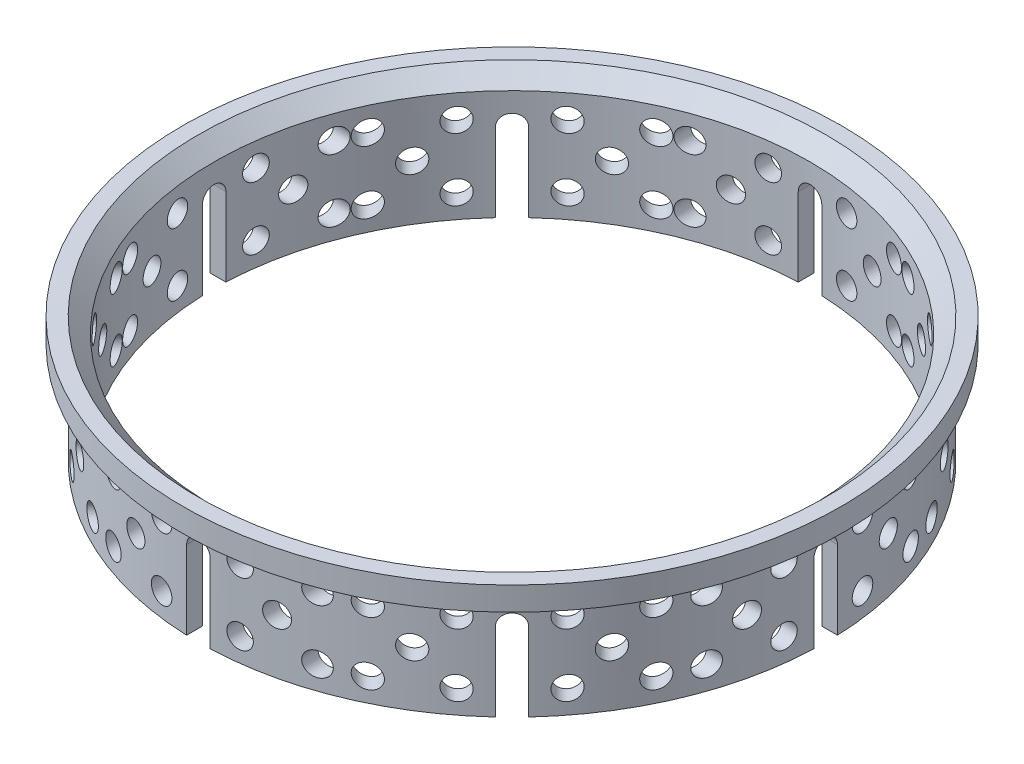
SolidWorks part; units mm, degrees
ref_plane "Front Plane" through (0, 0, 0) normal (0, 0, 1) x (1, 0, 0)
ref_plane "Top Plane" through (0, 0, 0) normal (0, 1, 0) x (1, 0, 0)
ref_plane "Right Plane" through (0, 0, 0) normal (1, 0, 0) x (0, 0, -1)
sketch "Sketch2" plane through (0, 0, 0) normal (0, 0, 1) x (1, 0, 0)
  line L0 (0, 0) -> (0, 28.4657) construction
  line L1 (0, 0) -> (48.26, 0) construction
  line L3 (53.34, 20.32) -> (53.34, 16.51)
  line L4 (53.34, 16.51) -> (50.8, 16.51)
  line L5 (50.8, 16.51) -> (50.8, 0)
  line L7 (48.26, 0) -> (50.8, 0)
  line L8 (48.26, 0) -> (48.26, 17.78)
  line L10 (53.34, 20.32) -> (50.8, 20.32)
  line L11 (50.8, 20.32) -> (48.26, 17.78)
  point P2 (0, 0)
  point P12 (0, 0)
  dimension "D1" = 48.26
  dimension "D2" = 17.78
  dimension "D3" = 2.54
  dimension "D4" = 3.81
  dimension "D5" = 2.54
  dimension "D6" = 2.54
revolve "Revolve1" add sketch "Sketch2" angle 360 about L0
ref_plane "Plane1" through (0, 0, 50.8) normal (0, 0, 1) x (1, 0, 0)
sketch "Sketch5" plane through (0, 0, 50.8) normal (0, 0, 1) x (1, 0, 0)
  line L0 (-1.905, 0) -> (1.905, 0)
  line L1 (-1.905, 0) -> (-1.905, 12.7)
  line L2 (1.905, 12.7) -> (1.905, 0)
  line L3 (-50.8, 0) -> (50.8, 0) construction
  line L4 (0, -11.176) -> (0, 11.176) construction
  arc A0 (-1.905, 12.7) -> (1.905, 12.7) centre (0, 12.7) cw
  circle A1 centre (-16.51, 13.97) radius 1.905
  circle A5 centre (-6.35, 13.97) radius 1.905
  circle A6 centre (-11.43, 8.89) radius 1.905
  circle A7 centre (-16.51, 3.81) radius 1.905
  circle A8 centre (-6.35, 3.81) radius 1.905
  circle A9 centre (16.51, 3.81) radius 1.905
  circle A10 centre (6.35, 3.81) radius 1.905
  circle A11 centre (11.43, 8.89) radius 1.905
  circle A12 centre (6.35, 13.97) radius 1.905
  circle A13 centre (16.51, 13.97) radius 1.905
  point P2 (0, 0)
  point P15 (0, 0)
  point P21 (-10.0631, 9.0586)
  dimension "D2" = 3.81
  dimension "D3" = 8.89
  dimension "D4" = 5.08
  dimension "D1" = 12.7
  dimension "D5" = 5.08
  dimension "D6" = 5.08
  dimension "D7" = 5.08
  dimension "D8" = 6.35
  dimension "D9" = 5.08
  dimension "D10" = 5.08
  dimension "D11" = 5.08
  dimension "D12" = 5.08
extrude "Cut-Extrude2" cut sketch "Sketch5" against normal up to surface (2.5776 mm away) up to face at (0, 0, -48.26)
pattern_circular "CirPattern1" count 8 over 360 about axis through (0, 0, 0) along (0, -1, 0) of "Cut-Extrude2"
